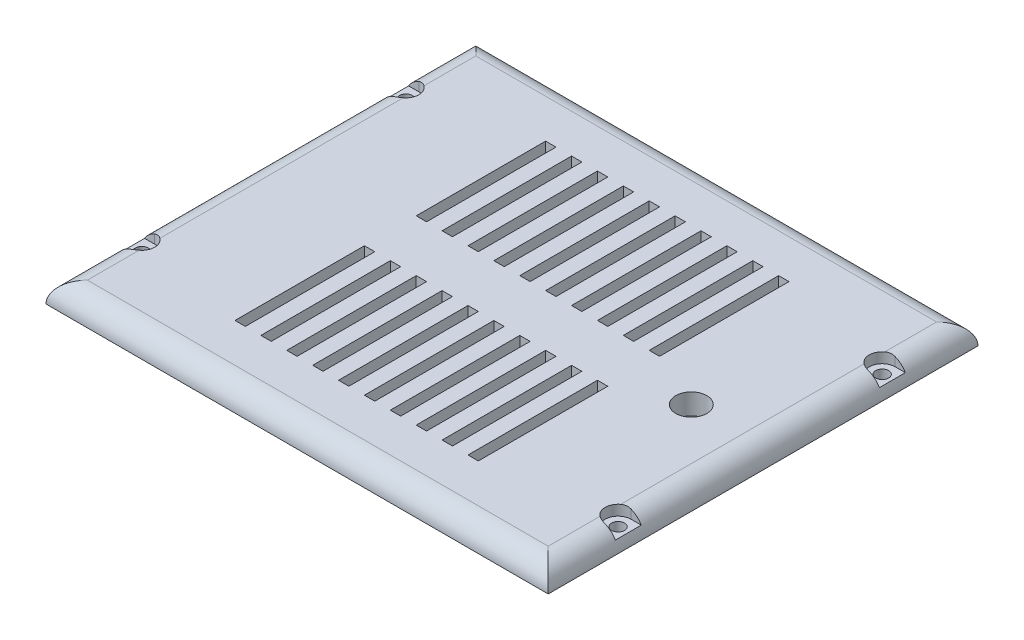
SolidWorks part; units mm, degrees
ref_plane "Front Plane" through (0, 0, 0) normal (0, 0, 1) x (1, 0, 0)
ref_plane "Top Plane" through (0, 0, 0) normal (0, 1, 0) x (1, 0, 0)
ref_plane "Right Plane" through (0, 0, 0) normal (1, 0, 0) x (0, 0, -1)
sketch "Sketch1" plane through (0, 0, 0) normal (0, 1, 0) x (1, 0, 0)
  line L1 (-45.0603, 26.9588) -> (51.9397, 26.9588)
  line L2 (-45.0603, 26.9588) -> (-45.0603, -56.0412)
  line L3 (-45.0603, -56.0412) -> (51.9397, -56.0412)
  line L4 (51.9397, 26.9588) -> (51.9397, -56.0412)
  dimension "D1" = 97
  dimension "D2" = 83
extrude "Boss-Extrude1" add sketch "Sketch1" along normal blind 4
fillet "Fillet1" radius 4 4 edges at (3.4397, 4, -26.9588) (51.9397, 4, 14.5412) (3.4397, 4, 56.0412) (-45.0603, 4, 14.5412)
sketch "Sketch3" plane through (0, 0, 0) normal (0, -1, 0) x (1, 0, 0)
  line L0 (-42.5603, 14.5412) -> (-42.5603, 40.0412) construction
  line L1 (-45.0603, 56.0412) -> (51.9397, 56.0412) construction
  line L2 (-42.5603, 40.0412) -> (49.4397, 40.0412) construction
  line L3 (-42.5603, 40.0412) -> (-42.5603, -10.9588) construction
  line L4 (-42.5603, -10.9588) -> (49.4397, -10.9588) construction
  line L5 (49.4397, 40.0412) -> (49.4397, -10.9588) construction
  line L6 (51.9397, 56.0412) -> (51.9397, -26.9588) construction
  circle A0 centre (-42.5603, 40.0412) radius 1.25
  circle A1 centre (49.4397, 40.0412) radius 1.25
  circle A2 centre (-42.5603, -10.9588) radius 1.25
  circle A3 centre (49.4397, -10.9588) radius 1.25
  dimension "D5" = 2.5
  dimension "D1" = 25.5
  dimension "D2" = 51
  dimension "D3" = 16
  dimension "D4" = 2.5
extrude "Cut-Extrude1" cut sketch "Sketch3" against normal blind 10
sketch "Sketch4" plane through (0, 4, 0) normal (0, 1, 0) x (1, 0, 0)
  line L1 (-42.5603, 13.4588) -> (-49.2065, 13.4588)
  line L3 (-42.5603, 8.4588) -> (-49.2065, 8.4588)
  line L4 (-49.2065, 13.4588) -> (-49.2065, 8.4588)
  line L5 (-42.5603, -37.5412) -> (-49.5542, -37.5412)
  line L7 (-42.5603, -42.5412) -> (-49.5542, -42.5412)
  line L8 (-49.5542, -37.5412) -> (-49.5542, -42.5412)
  line L9 (49.4397, 13.4588) -> (53.9737, 13.4588)
  line L11 (49.4397, 8.4588) -> (53.9737, 8.4588)
  line L12 (53.9737, 13.4588) -> (53.9737, 8.4588)
  line L13 (49.4397, -37.5412) -> (55.816, -37.5412)
  line L15 (49.4397, -42.5412) -> (55.816, -42.5412)
  line L16 (55.816, -37.5412) -> (55.816, -42.5412)
  arc A0 (-42.5603, 8.4588) -> (-42.5603, 13.4588) centre (-42.5603, 10.9588) ccw
  arc A1 (49.4397, 13.4588) -> (49.4397, 8.4588) centre (49.4397, 10.9588) ccw
  arc A2 (49.4397, -37.5412) -> (49.4397, -42.5412) centre (49.4397, -40.0412) ccw
  arc A3 (-42.5603, -42.5412) -> (-42.5603, -37.5412) centre (-42.5603, -40.0412) ccw
  dimension "D1" = 5
extrude "Cut-Extrude2" cut sketch "Sketch4" against normal blind 2
sketch "Sketch5" plane through (0, 4, 0) normal (0, 1, 0) x (1, 0, 0)
  line L0 (-41.0603, 15.4588) -> (-41.0603, -14.5412) construction
  line L1 (-41.0603, 8.9588) -> (-41.0603, -38.0412) construction
  line L2 (-41.0603, -14.5412) -> (-41.0603, -44.5412) construction
  line L3 (-41.0603, -14.5412) -> (47.9397, -14.5412) construction
  line L4 (47.9397, -38.0412) -> (47.9397, 8.9588) construction
  line L5 (-41.0603, 15.4588) -> (-20.0603, 15.4588) construction
  line L6 (-41.0603, -44.5412) -> (-20.0603, -44.5412) construction
  line L7 (-20.0603, 15.4588) -> (-18.0603, 15.4588)
  line L8 (-20.0603, 15.4588) -> (-20.0603, -9.5412)
  line L9 (-20.0603, -9.5412) -> (-18.0603, -9.5412)
  line L10 (-18.0603, 15.4588) -> (-18.0603, -9.5412)
  line L12 (-20.0603, -44.5412) -> (-18.0603, -44.5412)
  line L13 (-20.0603, -44.5412) -> (-20.0603, -19.5412)
  line L14 (-20.0603, -19.5412) -> (-18.0603, -19.5412)
  line L15 (-18.0603, -44.5412) -> (-18.0603, -19.5412)
  dimension "D1" = 89
  dimension "D2" = 21
  dimension "D3" = 30
  dimension "D4" = 2
  dimension "D5" = 25
  dimension "D6" = 21
  dimension "D7" = 25
  dimension "D8" = 2
extrude "Cut-Extrude3" cut sketch "Sketch5" against normal blind 10
pattern_linear "LPattern1" count 10 spacing 5 along (1, 0, 0) of "Cut-Extrude3"
sketch "Sketch6" plane through (0, 4, 0) normal (0, 1, 0) x (1, 0, 0)
  line L0 (47.9397, -14.5412) -> (-5.5667, -14.5412) construction
  line L1 (47.9397, -38.0412) -> (47.9397, 8.9588) construction
  circle A0 centre (38.0666, -14.5412) radius 3
  point P6 (0, 0)
  dimension "D1" = 6
extrude "Cut-Extrude4" cut sketch "Sketch6" against normal blind 105
